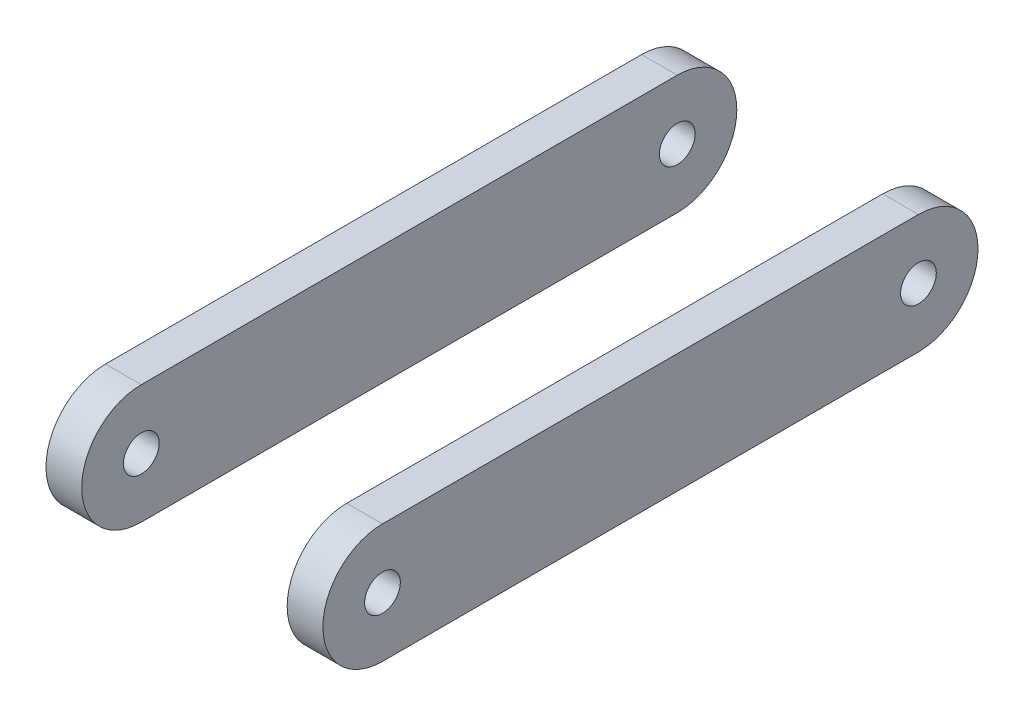
SolidWorks part; units mm, degrees
ref_plane "Front Plane" through (0, 0, 0) normal (0, 0, 1) x (1, 0, 0)
ref_plane "Top Plane" through (0, 0, 0) normal (0, 1, 0) x (1, 0, 0)
ref_plane "Right Plane" through (0, 0, 0) normal (1, 0, 0) x (0, 0, -1)
sketch "length (ref to equation file)" plane through (0, 0, 0) normal (1, 0, 0) x (0, 0, -1)
  line L0 (0, 0) -> (90, 0)
  dimension "D1" = 90
ref_axis "pivot w/ link 1" through (0, 0, 0) along (1, 0, 0)
ref_axis "pivot w/ platform" through (0, 0, -90) along (1, 0, 0)
ref_plane "Plane1" through (17.25, 0, 0) normal (1, 0, 0) x (0, 0, -1)
sketch "Sketch1" plane through (17.25, 0, 0) normal (1, 0, 0) x (0, 0, -1)
  line L0 (0, 0) -> (90, 0) construction
  line L1 (0, 10) -> (90, 10)
  line L2 (0, -10) -> (90, -10)
  arc A0 (0, 10) -> (0, -10) centre (0, 0) ccw
  arc A1 (90, -10) -> (90, 10) centre (90, 0) ccw
  point P4 (45, 0)
  dimension "D1" = 20
extrude "Boss-Extrude1" add sketch "Sketch1" along normal blind 6 contours L2 A1 L1 A0
sketch "Sketch2" plane through (23.25, 0, 0) normal (1, 0, 0) x (0, 0, -1)
  circle A0 centre (0, 0) radius 3
  circle A1 centre (0, 0) radius 3 construction
  circle A2 centre (90, 0) radius 3
extrude "Cut-Extrude1" cut sketch "Sketch2" against normal through all and the other way through all
mirror "Mirror4" about plane through (0, 0, 0) normal (1, 0, 0) of bodies 103
equation "\"link 2\"= 90mm"
equation "\"D1@length (ref to equation file)\" = \"link 2\""
equation "\"link 1 thickness\" = 6mm"
equation "\"beam width\" = 28.5mm"
equation "\"beam side wall thickness\" = 3mm"
equation "\"D1@Plane1\" = \"link 2 plane\""
equation "\"link 2 plane\"= \"beam side wall thickness\" + \"beam width\" / 2"
equation "\"motor center z\" = 60mm"
equation "\"motor center y\" = 20mm"
equation "\"link 1\" = 40mm"
equation "\"pivot height\"= 140mm"
equation "\"beam length\" = 120mm"
equation "\"camera height\" = 250mm"
equation "\"link height\" = 20mm"
equation "\"D1@Sketch1\"=\"link height\""
equation "\"D1@Boss-Extrude1\"=\"link 1 thickness\""
